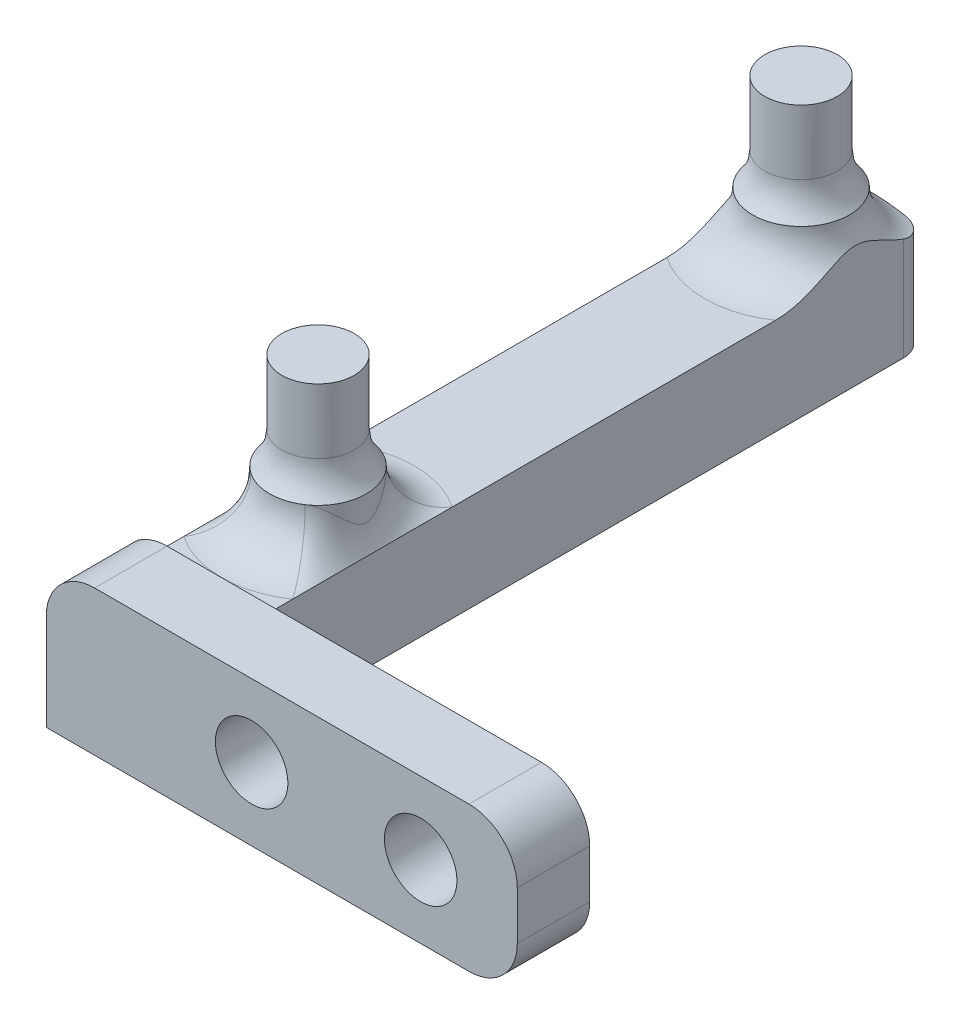
SolidWorks part; units mm, degrees
ref_plane "Front Plane" through (0, 0, 0) normal (0, 0, 1) x (1, 0, 0)
ref_plane "Top Plane" through (0, 0, 0) normal (0, 1, 0) x (1, 0, 0)
ref_plane "Right Plane" through (0, 0, 0) normal (1, 0, 0) x (0, 0, -1)
sketch "Sketch1" plane through (0, 0, 0) normal (0, 1, 0) x (1, 0, 0)
  line L0 (0, 0) -> (0, 15.9628) construction
  line L2 (-2.25, 17.3926) -> (2.25, 17.3926)
  line L3 (-2.25, 17.3926) -> (-2.25, -8.6074)
  line L4 (-2.25, -8.6074) -> (2.25, -8.6074)
  line L5 (2.25, 17.3926) -> (2.25, -8.6074)
  line L6 (-2.25, -8.6074) -> (2.25, -8.6074)
  line L7 (-2.25, -8.6074) -> (-2.25, -14.6074)
  line L8 (-2.25, -14.6074) -> (2.25, -14.6074)
  line L9 (2.25, -8.6074) -> (2.25, -14.6074)
  circle A0 centre (0, 14.3926) radius 2
  circle A1 centre (0, -5.6074) radius 2
  dimension "D1" = 2.25
  dimension "D3" = 4
  dimension "D4" = 4
  dimension "D5" = 3
  dimension "D6" = 3
  dimension "D7" = 20
  dimension "D2" = 4.5
  dimension "D8" = 6
extrude "Boss-Extrude1" add sketch "Sketch1" along normal blind 4 contours L9 L4 L7 L8 | A0 L2 L3 L4 L5 A1 region at (0, 0, -4.3926) region at (0, 0, 11.6074)
extrude "Boss-Extrude2" add sketch "Sketch1<3>" along normal blind 6 contours A1 | A0 L0 | L0 A0 region at (0, 0, -14.3926) region at (0, 0, 5.6074)
sketch "Sketch1<3>" plane through (0, 0, 0) normal (0, 1, 0) x (1, 0, 0) same geometry as "Sketch1"
sketch "Sketch2" plane through (0, 6, 0) normal (0, 1, 0) x (1, 0, 0)
  circle A0 centre (0, 14.3926) radius 1.5
  circle A1 centre (0, -5.6074) radius 1.5
  dimension "D1" = 3
  dimension "D2" = 3
extrude "Boss-Extrude3" add sketch "Sketch2" along normal blind 4
fillet "Fillet1" radius 2 1 edges at (0, 6, 7.1074)
fillet "Fillet2" radius 2 1 edges at (0, 6, -12.8926)
fillet "Fillet3" radius 2 1 edges at (0, 4, 7.6074)
fillet "Fillet4" radius 2 1 edges at (0, 4, -12.3926)
sketch "Sketch3" plane through (2.25, 0, 0) normal (1, 0, 0) x (0, 0, -1)
  line L0 (17.3926, 0) -> (-14.6074, 0) construction
  line L1 (-14.6074, 4) -> (-11.6074, 4)
  line L2 (-14.6074, 4) -> (-14.6074, 0)
  line L3 (-14.6074, 0) -> (-11.6074, 0)
  line L4 (-11.6074, 4) -> (-11.6074, 0)
  dimension "D1" = 3
extrude "Boss-Extrude4" add sketch "Sketch3" along normal blind 15
sketch "Sketch5" plane through (0, 4, 0) normal (0, 1, 0) x (1, 0, 0)
  line L0 (-2.25, -14.6074) -> (17.25, -14.6074) construction
  line L1 (-2.25, -14.6074) -> (2.25, -14.6074)
  line L2 (-2.25, -14.6074) -> (-2.25, -11.6074)
  line L3 (-2.25, -11.6074) -> (2.25, -11.6074)
  line L4 (2.25, -14.6074) -> (2.25, -11.6074)
extrude "Boss-Extrude5" add sketch "Sketch5" along normal blind 2
sketch "Sketch7" plane through (2.25, 0, 0) normal (1, 0, 0) x (0, 0, -1)
  line L1 (-11.6074, 6) -> (-14.6074, 6)
  line L2 (-11.6074, 6) -> (-11.6074, 4)
  line L3 (-11.6074, 4) -> (-14.6074, 4)
  line L4 (-14.6074, 6) -> (-14.6074, 4)
extrude "Boss-Extrude6" add sketch "Sketch7" along normal up to surface (15 mm away) up to face at (17.25, 2, 13.1074)
sketch "Sketch8" plane through (0, 0, 11.6074) normal (0, 0, -1) x (-1, 0, 0)
  line L0 (-17.25, 3) -> (4.7513, 3) construction
  line L1 (-17.25, 0) -> (-17.25, 6) construction
  line L2 (-2.25, 0) -> (-2.25, 4) construction
  circle A0 centre (-6.25, 3) radius 1.5
  circle A1 centre (-13.25, 3) radius 1.5
  dimension "D1" = 3
  dimension "D2" = 3
  dimension "D3" = 4
  dimension "D4" = 4
extrude "Cut-Extrude1" cut sketch "Sketch8" against normal through all
fillet "Fillet12" radius 2 2 edges at (2.25, 2, 11.6074) (0, 4, 11.6074)
fillet "Fillet13" radius 2 1 edges at (-2.25, 6, 13.1074)
fillet "Fillet14" radius 2 2 edges at (17.25, 6, 13.1074) (17.25, 0, 13.1074)
fillet "Fillet16" radius 1 2 edges at (-2.25, 2.0078, -17.3926) (2.25, 2.0078, -17.3926)
